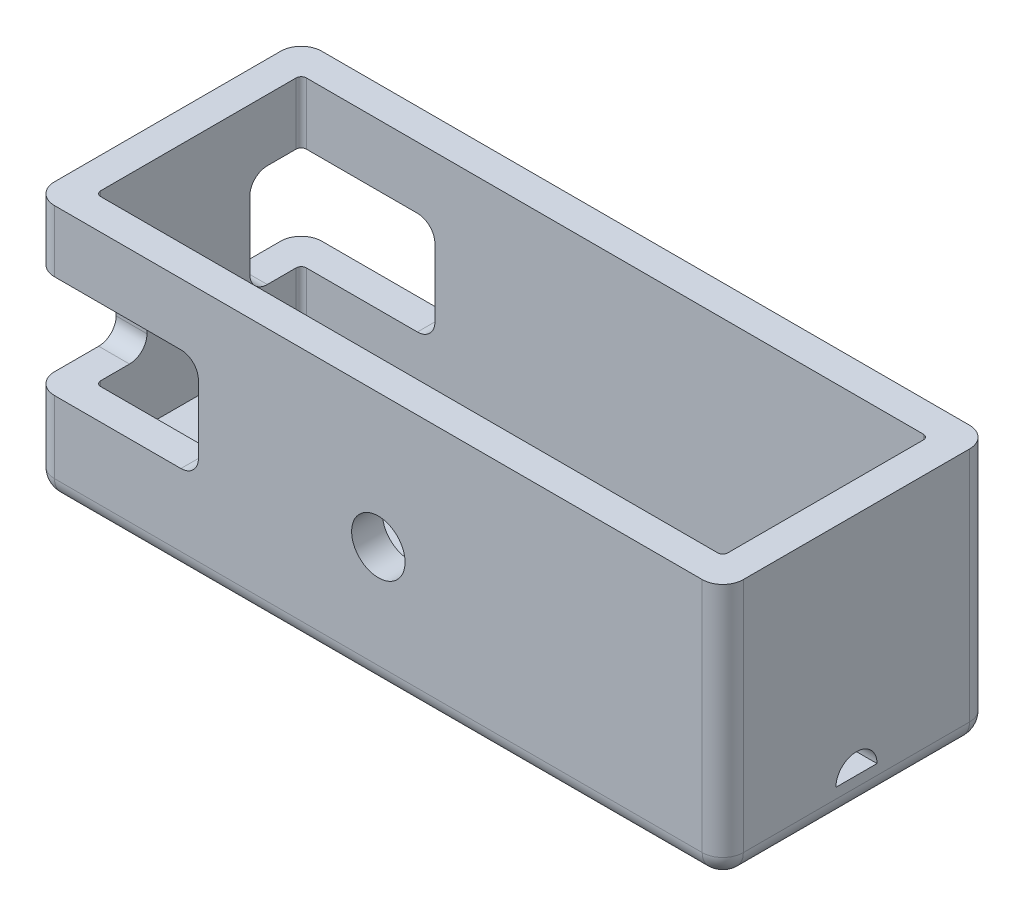
SolidWorks part; units mm, degrees
ref_plane "Front Plane" through (0, 0, 0) normal (0, 0, 1) x (1, 0, 0)
ref_plane "Top Plane" through (0, 0, 0) normal (0, 1, 0) x (1, 0, 0)
ref_plane "Right Plane" through (0, 0, 0) normal (1, 0, 0) x (0, 0, -1)
sketch "Sketch1" plane through (0, 0, 0) normal (0, 1, 0) x (1, 0, 0)
  line L0 (-30.5, 10) -> (-30.5, 13) construction
  line L1 (33.5, -13) -> (-33.5, -13)
  line L2 (33.5, -13) -> (33.5, 13)
  line L3 (33.5, 13) -> (-33.5, 13)
  line L4 (-33.5, -13) -> (-33.5, 13)
  line L5 (0, 13) -> (0, -13) construction
  line L6 (33.5, 0) -> (-33.5, 0) construction
  line L7 (30.5, -10) -> (-30.5, -10)
  line L8 (30.5, -10) -> (30.5, 10)
  line L9 (30.5, 10) -> (-30.5, 10)
  line L10 (-30.5, -10) -> (-30.5, 10)
  line L11 (0, 10) -> (0, -10) construction
  line L12 (30.5, 0) -> (-30.5, 0) construction
  line L13 (-30.5, 10) -> (-33.5, 10) construction
  point P0 (0, 0)
  point P4 (0, 0)
  dimension "D1" = 20
  dimension "D2" = 61
  dimension "D3" = 3
extrude "Boss-Extrude1" add sketch "Sketch1" against normal blind 3 contours L10 L7 L8 L9 | L4 L1 L2 L3 L7 L10 L9 L8 region at (0, 0, 12.2813) region at (0, 0, 0)
extrude "Boss-Extrude2" add sketch "Sketch1<3>" along normal blind 22
sketch "Sketch1<3>" plane through (0, 0, 0) normal (0, 1, 0) x (1, 0, 0) same geometry as "Sketch1"
fillet "Fillet1" radius 2 8 edges at (0, -3, 13) (33.5, -3, 0) (0, -3, -13) (-33.5, -3, 0) (-33.5, 9.5, -13) (-33.5, 9.5, 13) (33.5, 9.5, 13) (33.5, 9.5, -13)
fillet "Fillet2" radius 0.5 4 edges at (30.5, 11, -10) (-30.5, 11, -10) (30.5, 11, 10) (-30.5, 11, 10)
sketch "Sketch2" plane through (33.5, 0, 0) normal (1, 0, 0) x (0, 0, -1)
  line L1 (-2, 0) -> (2, 0)
  line L2 (-9.5, 0) -> (9.5, 0) construction
  line L3 (-9.5, 0) -> (9.5, 0) construction
  arc A0 (-2, 0) -> (2, 0) centre (0, 0) cw
  dimension "D1" = 2
extrude "Cut-Extrude1" cut sketch "Sketch2" against normal up to surface (3 mm away) contours A0 L1 region at (33.5, 0.8488, 0) up to face at (30.5, 11, 0)
sketch "Sketch3" plane through (0, 0, 0) normal (0, 1, 0) x (1, 0, 0)
  line L0 (-33.5, 0) -> (33.5, 0) construction
  line L1 (-33.5, 11) -> (-33.5, -11) construction
  line L2 (33.5, -11) -> (33.5, 11) construction
  line L3 (30.5, 2) -> (30.5, 9.5) construction
  line L4 (30.5, -9.5) -> (30.5, 9.5) construction
  circle A0 centre (19.4, 0) radius 1.1
  circle A1 centre (-4.6, 0) radius 1.1
  dimension "D1" = 2.2
  dimension "D2" = 2.2
  dimension "D3" = 11.1
  dimension "D4" = 35.1
extrude "Cut-Extrude2" cut sketch "Sketch3" against normal through all
sketch "Sketch4" plane through (0, 0, 13) normal (0, 0, 1) x (1, 0, 0)
  line L0 (-30, 0) -> (30, 0) construction
  line L1 (-17.5, 6) -> (-33.5, 6)
  line L2 (-17.5, 6) -> (-17.5, 16)
  line L3 (-17.5, 16) -> (-33.5, 16)
  line L4 (-33.5, 6) -> (-33.5, 16)
  line L5 (-25.5, 16) -> (-25.5, 6) construction
  line L6 (-17.5, 11) -> (-33.5, 11) construction
  line L7 (30.5, 0) -> (30.5, 22) construction
  line L9 (-33.5, -1) -> (-33.5, 22) construction
  point P0 (-25.5, 11)
  dimension "D1" = 11
  dimension "D2" = 10
  dimension "D3" = 48
extrude "Cut-Extrude3" cut sketch "Sketch4" against normal blind 8
extrude "Cut-Extrude7" cut sketch "Sketch4<2>" along normal blind 8 from surface starting at face at (0, 10.5, -13)
sketch "Sketch4<2>" plane through (0, 0, 13) normal (0, 0, 1) x (1, 0, 0) same geometry as "Sketch4"
sketch "Sketch6" plane through (0, -3, 0) normal (0, -1, 0) x (1, 0, 0)
  circle A0 centre (-4.6, 0) radius 3
  circle A1 centre (19.4, 0) radius 3
  dimension "D2" = 6
extrude "Cut-Extrude5" cut sketch "Sketch6" against normal blind 1.5
sketch "Sketch7" plane through (0, 0, 0) normal (1, 0, 0) x (0, 0, -1)
  line L0 (-13, -3) -> (-11, -3)
  line L5 (-13, -1) -> (-13, 22) construction
  line L7 (-13, 9.5) -> (13, 9.5) construction
  line L8 (13, 22) -> (13, -1) construction
  line L9 (13, 22) -> (13, -3) construction
  line L10 (11, -3) -> (-11, -3) construction
  line L11 (-18.5981, 1.5) -> (-13, 11.1962)
  line L12 (-13, -3) -> (-16, -3)
  line L13 (-13, 3) -> (-19, 3)
  line L14 (-13, -3) -> (-13, 3)
  line L15 (-13, 11.1962) -> (-13, 3)
  line L16 (-19, 0) -> (-19, 3)
  arc A2 (-11, -3) -> (-13, -1) centre (-11, -1) cw
  arc A3 (-19, 0) -> (-14.6584, 2.6833) centre (-16, 0) cw
  arc A4 (-19, 0) -> (-16, -3) centre (-16, 0) ccw
  circle A5 centre (-16, 0) radius 2
  dimension "D1" = 6
  dimension "D5" = 30
  dimension "D3" = 4
  dimension "D4" = 1
  dimension "D2" = 6
extrude "Boss-Extrude3" [suppressed] add sketch "Sketch7" along normal blind 5 from offset 5.2 contours L15 L11 L13 | A3 A4 L12 L14 L13 A5 | L0 A2 L14 | L11 A3 L13
mirror "Mirror1" [suppressed] about plane through (0, 0, 0) normal (1, 0, 0)
sketch "Sketch9" plane through (0, -3, 0) normal (0, -1, 0) x (1, 0, 0)
  line L0 (31.5, -13) -> (-31.5, -13) construction
  line L1 (-17, -13) -> (17, -13)
  line L2 (-17, -13) -> (-17, -13.5)
  line L3 (-14, -16.5) -> (14, -16.5)
  line L4 (17, -13) -> (17, -13.5)
  line L6 (-15, -13) -> (15, -13)
  line L7 (-15, -13) -> (-15, -13.5)
  line L8 (-14, -14.5) -> (14, -14.5)
  line L9 (15, -13) -> (15, -13.5)
  arc A0 (-14, -14.5) -> (-15, -13.5) centre (-14, -13.5) cw
  arc A1 (14, -14.5) -> (15, -13.5) centre (14, -13.5) ccw
  arc A2 (14, -16.5) -> (17, -13.5) centre (14, -13.5) ccw
  arc A3 (-14, -16.5) -> (-17, -13.5) centre (-14, -13.5) cw
  point P10 (0, -14.5)
  point P11 (0, -16.5)
  dimension "D5" = 1
  dimension "D1" = 1.5
  dimension "D2" = 2
  dimension "D3" = 2
  dimension "D4" = 30
extrude "Boss-Extrude4" add sketch "Sketch9" against normal blind 3 from vertex contours A3 L3 A2 L4 L1 L9 A1 L8 A0 L7 L2 region at (0, -3, -15.3257) starting at point (31.5, -1, -13)
fillet "Fillet4" radius 0.5 20 edges at (-15, 2, -13.25) (-14.7071, 2, -14.2071) (15, 2, -13.25) (14.7071, 2, -14.2071) (-17, -1, -13.25) (-16.1213, -1, -15.6213) (17, -1, -13.25) (16.1213, -1, -15.6213) (-17, 2, -13.25) (-16.1213, 2, -15.6213) (17, 2, -13.25) (16.1213, 2, -15.6213) (-15, -1, -13.25) (-14.7071, -1, -14.2071) (15, -1, -13.25) (14.7071, -1, -14.2071) (0, 2, -14.5) (0, -1, -16.5) (0, 2, -16.5) (0, -1, -14.5)
fillet "Fillet5" radius 0.5 16 edges at (16.8536, 1.8536, -13) (16, 2, -13) (15.1464, 1.8536, -13) (15, 0.5, -13) (15.1464, -0.8536, -13) (-16, -1, -13) (16, -1, -13) (16.8536, -0.8536, -13) (-15.1464, 1.8536, -13) (-16, 2, -13) (-16.8536, 1.8536, -13) (-17, 0.5, -13) (-16.8536, -0.8536, -13) (-15.1464, -0.8536, -13) (17, 0.5, -13) (-15, 0.5, -13)
sketch "Sketch10" plane through (0, 0, 13) normal (0, 0, 1) x (1, 0, 0)
  line L0 (-31.5, -1) -> (31.5, -1) construction
  circle A0 centre (0, 9) radius 2.6
  dimension "D1" = 5.2
  dimension "D2" = 10
extrude "Cut-Extrude6" cut sketch "Sketch10" against normal up to surface (3 mm away) and the other way through all contours A0 up to face at (-11.875, 11, 10)
fillet "Fillet6" radius 1.7 8 edges at (-17.5, 6, 11.5) (-32, 6, 5) (-32, 16, 5) (-17.5, 16, 11.5) (-17.5, 6, -11.5) (-32, 6, -5) (-32, 16, -5) (-17.5, 16, -11.5)
